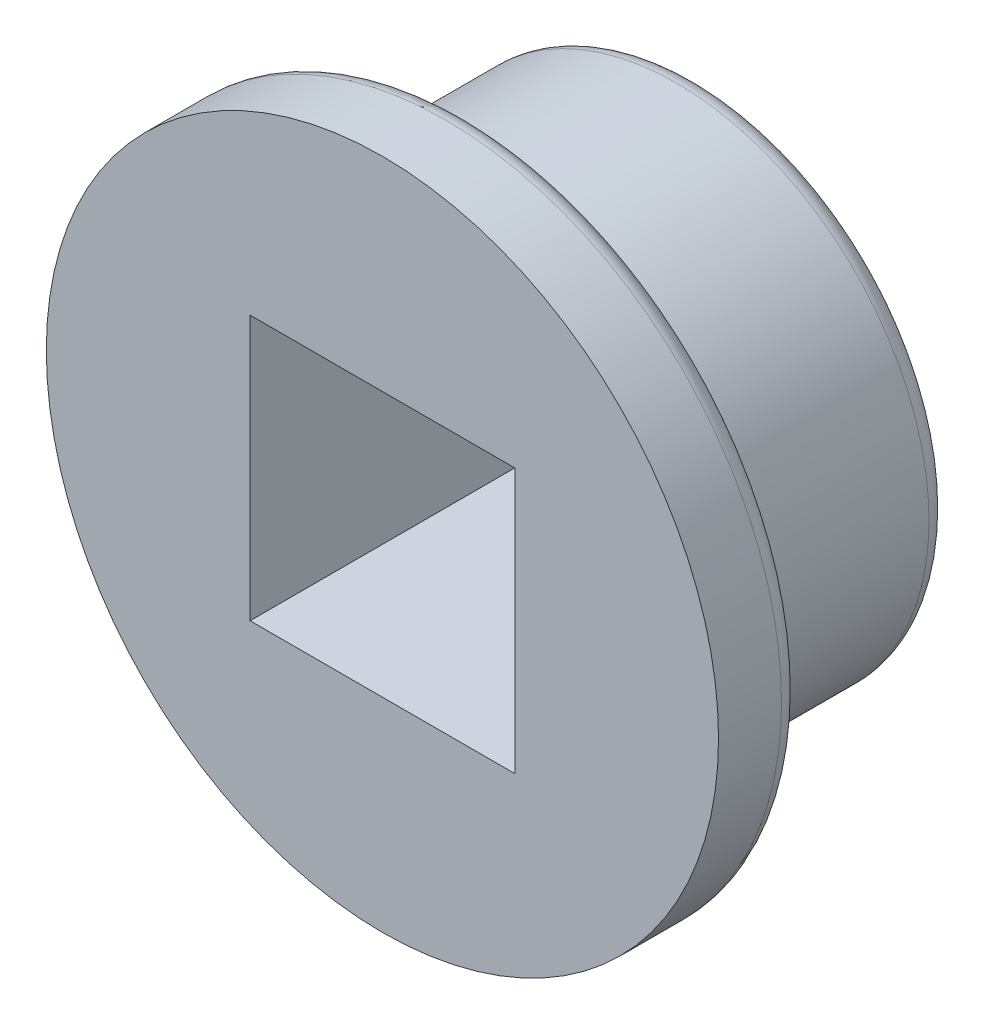
SolidWorks part; units mm, degrees
material "ABS"
ref_plane "Front Plane" through (0, 0, 0) normal (0, 0, 1) x (1, 0, 0)
ref_plane "Top Plane" through (0, 0, 0) normal (0, 1, 0) x (1, 0, 0)
ref_plane "Right Plane" through (0, 0, 0) normal (1, 0, 0) x (0, 0, -1)
sketch "Sketch1" plane through (0, 0, 0) normal (0, 0, 1) x (1, 0, 0)
  line L1 (-3.15, 3.15) -> (3.15, 3.15)
  line L2 (-3.15, 3.15) -> (-3.15, -3.15)
  line L3 (-3.15, -3.15) -> (3.15, -3.15)
  line L4 (3.15, 3.15) -> (3.15, -3.15)
  circle A0 centre (0, 0) radius 6.01
  circle A1 centre (0, 0) radius 8
  point P4 (0, 3.15)
  point P6 (-3.15, 0)
  dimension "D2" = 12.02
  dimension "D3" = 16
  dimension "D1" = 6.3
extrude "Boss-Extrude1" add sketch "Sketch1" against normal blind 5.5 contours A0 L1 L4 L3 L2 region at (-5.84, 0, 0)
extrude "Boss-Extrude2" add sketch "Sketch1<3>" along normal blind 2 contours A1 A0 | A0 L1 L4 L3 L2 region at (-5.84, 0, 0) region at (-7.7737, 0, 0)
sketch "Sketch1<3>" plane through (0, 0, 0) normal (0, 0, 1) x (1, 0, 0) same geometry as "Sketch1"
fillet "Fillet1" radius 0.5 2 edges at (8, 0, 0) (6.01, 0, -5.5)
